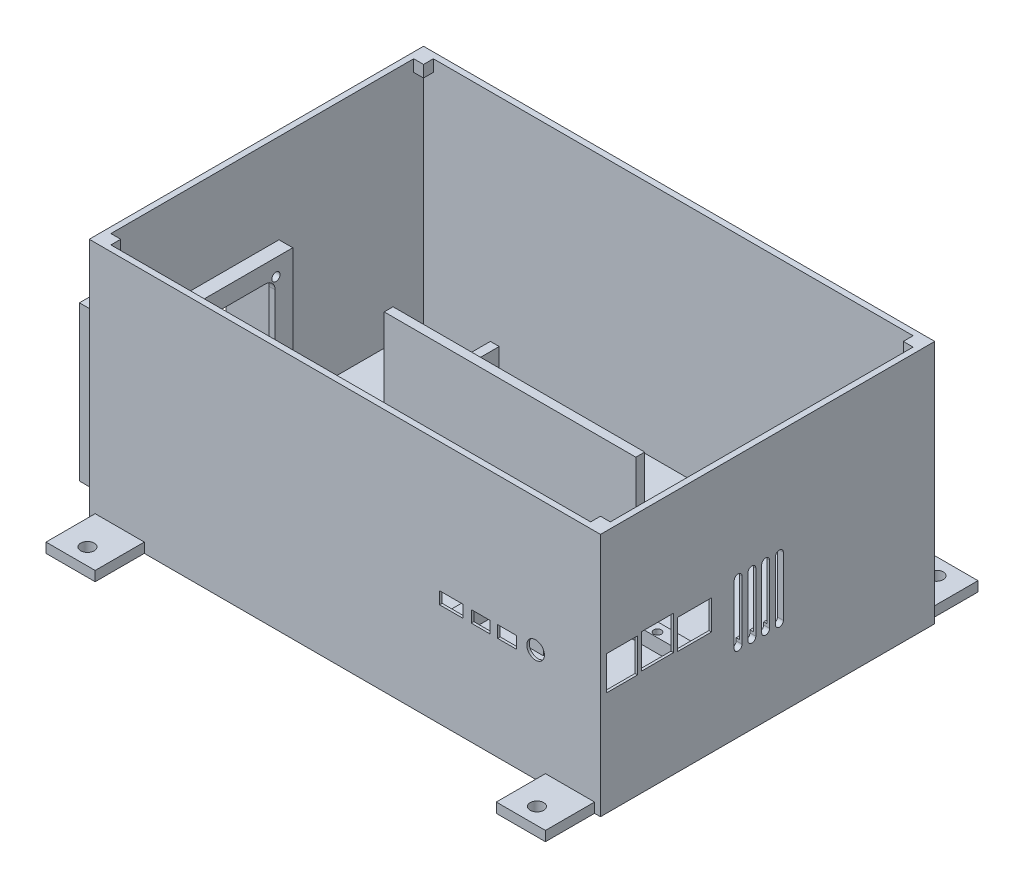
SolidWorks part; units mm, degrees
ref_plane "Front Plane" through (0, 0, 0) normal (0, 0, 1) x (1, 0, 0)
ref_plane "Top Plane" through (0, 0, 0) normal (0, 1, 0) x (1, 0, 0)
ref_plane "Right Plane" through (0, 0, 0) normal (1, 0, 0) x (0, 0, -1)
sketch "Sketch1" plane through (0, 0, 0) normal (0, 1, 0) x (1, 0, 0)
  line L1 (-130, -85) -> (130, -85)
  line L2 (-130, -85) -> (-130, 85)
  line L3 (-130, 85) -> (130, 85)
  line L4 (130, -85) -> (130, 85)
  line L5 (-130, -85) -> (130, 85) construction
  line L6 (-130, 85) -> (130, -85) construction
  point P0 (0, 0)
  dimension "D1" = 170
  dimension "D2" = 260
extrude "Floor" add sketch "Sketch1" along normal blind 4.3805
sketch "Sketch2" plane through (0, 4.3805, 0) normal (0, 1, 0) x (1, 0, 0)
  line L0 (127, -82) -> (127, 82)
  line L1 (127, 82) -> (-127, 82)
  line L2 (-127, 82) -> (-127, -82)
  line L3 (-127, -82) -> (127, -82)
  line L4 (130, -85) -> (130, 85)
  line L5 (130, 85) -> (-130, 85)
  line L6 (-130, 85) -> (-130, -85)
  line L7 (-130, -85) -> (130, -85)
  line L8 (130, -85) -> (130, 85)
  line L9 (130, 85) -> (-130, 85)
  line L10 (-130, 85) -> (-130, -85)
  line L11 (-130, -85) -> (130, -85)
  dimension "D1" = 0
  dimension "D2" = 3
extrude "Wall" add sketch "Sketch2" along normal blind 120
sketch "Sketch4" plane through (0, 4.3805, 0) normal (0, 1, 0) x (1, 0, 0)
  line L0 (120, -33) -> (49, -33)
  line L1 (127, -82) -> (42, -82)
  line L2 (127, -82) -> (127, -26)
  line L3 (127, -26) -> (42, -26)
  line L4 (42, -82) -> (42, -26)
  line L5 (49, -75) -> (49, -33)
  line L6 (120, -75) -> (49, -75)
  line L7 (120, -75) -> (120, -33)
  dimension "D1" = 85
  dimension "D2" = 56
  dimension "D3" = 7
extrude "Rpi stand" add sketch "Sketch4" along normal blind 7 from offset 30
sketch "Sketch7" plane through (0, 124.3805, 0) normal (0, 1, 0) x (1, 0, 0)
sketch "Sketch3" plane through (0, 0, 0) normal (0, 1, 0) x (1, 0, 0)
  line L0 (-114.3, 101.6) -> (114.3, 101.6) construction
  line L1 (-127, 85) -> (-102, 85)
  line L2 (-127, 85) -> (-127, 110)
  line L3 (-127, 110) -> (-102, 110)
  line L4 (-102, 85) -> (-102, 110)
  line L5 (127, 85) -> (102, 85)
  line L6 (127, 85) -> (127, 110)
  line L7 (127, 110) -> (102, 110)
  line L8 (102, 85) -> (102, 110)
  line L9 (-127, -85) -> (-102, -85)
  line L10 (-127, -85) -> (-127, -110)
  line L11 (-127, -110) -> (-102, -110)
  line L12 (-102, -85) -> (-102, -110)
  line L13 (127, -85) -> (102, -85)
  line L14 (127, -85) -> (127, -110)
  line L15 (127, -110) -> (102, -110)
  line L16 (102, -85) -> (102, -110)
  line L17 (114.3, 101.6) -> (114.3, -101.6) construction
  line L18 (114.3, -101.6) -> (-114.3, -101.6) construction
  line L19 (-114.3, -101.6) -> (-114.3, 101.6) construction
  line L20 (-130, 0) -> (130, 0) construction
  line L21 (130, 85) -> (-130, 85) construction
  line L22 (130, -85) -> (130, 85) construction
  line L23 (0, 101.6) -> (0, -101.6) construction
  line L26 (-130, 85) -> (-130, -85) construction
  line L27 (-130, -85) -> (130, -85) construction
  circle A0 centre (-114.3, 101.6) radius 3.429
  circle A1 centre (114.3, 101.6) radius 3.429
  circle A2 centre (114.3, -101.6) radius 3.429
  circle A3 centre (-114.3, -101.6) radius 3.429
  point P4 (-130, -85)
  point P9 (130, -85)
  point P28 (-114.5, -85)
  point P29 (-102, -97.5)
  point P30 (114.5, -85)
  point P31 (-102, 97.5)
  dimension "D5" = 6.858
  dimension "D1" = 25
  dimension "D2" = 25
  dimension "D3" = 25
  dimension "D6" = 203.2
  dimension "D7" = 228.6
  dimension "D8" = 3
  dimension "D9" = 3
  dimension "D4" = 25
extrude "Brackets" add sketch "Sketch3" along normal blind 5
sketch "Sketch5" plane through (-130, 0, 0) normal (-1, 0, 0) x (0, 0, 1)
  line L0 (-8.5, 78.8805) -> (70, 78.8805)
  line L1 (-1, 4.3805) -> (62.5, 4.3805)
  line L2 (-4.5, 7.8805) -> (-4.5, 71.3805)
  line L3 (-1, 74.8805) -> (62.5, 74.8805)
  line L4 (66, 7.8805) -> (66, 71.3805)
  line L5 (70, 0.3805) -> (70, 78.8805)
  line L6 (-8.5, 0.3805) -> (70, 0.3805)
  line L7 (-8.5, 0.3805) -> (-8.5, 78.8805)
  line L8 (-4.5, 4.3805) -> (66, 4.3805) construction
  line L9 (110, 5) -> (110, 0) construction
  line L10 (-4.5, 4.3805) -> (-4.5, 74.8805) construction
  line L11 (-82, 4.3805) -> (82, 4.3805) construction
  line L12 (66, 4.3805) -> (66, 74.8805) construction
  line L13 (-4.5, 74.8805) -> (66, 74.8805) construction
  arc A0 (-1, 4.3805) -> (-4.5, 7.8805) centre (-1, 7.8805) cw
  arc A1 (62.5, 4.3805) -> (66, 7.8805) centre (62.5, 7.8805) ccw
  arc A2 (62.5, 74.8805) -> (66, 71.3805) centre (62.5, 71.3805) cw
  arc A3 (-4.5, 71.3805) -> (-1, 74.8805) centre (-1, 71.3805) cw
  dimension "D4" = 3.5
  dimension "D1" = 70.5
  dimension "D2" = 70.5
  dimension "D5" = 40
  dimension "D3" = 4
extrude "Fan Holder" add sketch "Sketch5" along normal blind 20 and the other way blind 10
sketch "Sketch8" plane through (-130, 0, 0) normal (-1, 0, 0) x (0, 0, 1)
  line L4 (-4.5, 71.3805) -> (-4.5, 7.8805)
  line L5 (-1, 4.3805) -> (62.5, 4.3805)
  line L6 (66, 7.8805) -> (66, 71.3805)
  line L7 (62.5, 74.8805) -> (-1, 74.8805)
  line L8 (-4.5, 71.3805) -> (-4.5, 7.8805)
  line L9 (-1, 4.3805) -> (62.5, 4.3805)
  line L10 (66, 7.8805) -> (66, 71.3805)
  line L23 (62.5, 74.8805) -> (-1, 74.8805)
  arc A2 (-4.5, 7.8805) -> (-1, 4.3805) centre (-1, 7.8805) ccw
  arc A3 (-4.5, 7.8805) -> (-1, 4.3805) centre (-1, 7.8805) ccw
  arc A4 (62.5, 4.3805) -> (66, 7.8805) centre (62.5, 7.8805) ccw
  arc A5 (62.5, 4.3805) -> (66, 7.8805) centre (62.5, 7.8805) ccw
  arc A8 (66, 71.3805) -> (62.5, 74.8805) centre (62.5, 71.3805) ccw
  arc A14 (66, 71.3805) -> (62.5, 74.8805) centre (62.5, 71.3805) ccw
  arc A16 (-1, 74.8805) -> (-4.5, 71.3805) centre (-1, 71.3805) ccw
  arc A17 (-1, 74.8805) -> (-4.5, 71.3805) centre (-1, 71.3805) ccw
  dimension "D1" = 0
extrude "Fan hole" cut sketch "Sketch8" against normal up to next
sketch "Sketch11" plane through (-120, 0, 0) normal (-1, 0, 0) x (0, 0, 1)
  line L0 (-8.5, 39.6305) -> (70, 39.6305) construction
  line L1 (30.75, 78.8805) -> (30.75, 0.3805) construction
  line L3 (0.05, 8.9305) -> (61.45, 8.9305) construction
  line L4 (-8.5, 78.8805) -> (-8.5, 0.3805)
  line L5 (-8.5, 0.3805) -> (70, 0.3805)
  line L6 (70, 0.3805) -> (70, 78.8805)
  line L7 (70, 78.8805) -> (-8.5, 78.8805)
  line L8 (-8.5, 78.8805) -> (-8.5, 0.3805)
  line L9 (-8.5, 0.3805) -> (70, 0.3805)
  line L10 (70, 0.3805) -> (70, 78.8805)
  line L11 (70, 78.8805) -> (-8.5, 78.8805)
  line L12 (0.05, 8.9305) -> (0.05, 70.3305) construction
  line L13 (0.05, 70.3305) -> (61.45, 70.3305) construction
  line L14 (61.45, 8.9305) -> (61.45, 70.3305) construction
  line L15 (0.05, 8.9305) -> (61.45, 70.3305) construction
  line L16 (0.5, 69.8805) -> (0.5, 9.3805)
  line L17 (0.5, 9.3805) -> (61, 9.3805)
  line L18 (61, 9.3805) -> (61, 69.8805)
  line L19 (61, 69.8805) -> (0.5, 69.8805)
  line L20 (0.5, 64.8805) -> (0.5, 14.3805)
  line L21 (5.5, 9.3805) -> (56, 9.3805)
  line L22 (61, 14.3805) -> (61, 64.8805)
  line L23 (56, 69.8805) -> (5.5, 69.8805)
  line L24 (0.05, 70.3305) -> (61.45, 8.9305) construction
  arc A0 (0.5, 14.3805) -> (5.5, 9.3805) centre (5.5, 14.3805) ccw
  arc A1 (56, 9.3805) -> (61, 14.3805) centre (56, 14.3805) ccw
  arc A2 (61, 64.8805) -> (56, 69.8805) centre (56, 64.8805) ccw
  arc A3 (0.5, 64.8805) -> (5.5, 69.8805) centre (5.5, 64.8805) cw
  circle A4 centre (0.05, 70.3305) radius 2.1
  circle A5 centre (61.45, 70.3305) radius 2.1
  circle A6 centre (61.45, 8.9305) radius 2.1
  circle A7 centre (0.05, 8.9305) radius 2.1
  point P24 (30.75, 39.6305)
  point P34 (30.75, 39.6305)
  dimension "D3" = 5
  dimension "D6" = 4.2
  dimension "D4" = 61.4
  dimension "D5" = 61.4
  dimension "D1" = 0
  dimension "D2" = 9
extrude "Boss-Extrude9" add sketch "Sketch11" along normal blind 3
sketch "Sketch12" plane through (0, 34.3805, 0) normal (0, -1, 0) x (1, 0, 0)
  line L1 (42, 26) -> (49, 26)
  line L2 (42, 26) -> (42, 33)
  line L3 (42, 33) -> (49, 33)
  line L4 (49, 26) -> (49, 33)
  dimension "D1" = 7
  dimension "D2" = 7
extrude "Boss-Extrude10" add sketch "Sketch12" along normal up to next
sketch "Sketch13" plane through (0, 4.3805, 0) normal (0, 1, 0) x (1, 0, 0)
  line L0 (127, 82) -> (-127, 82) construction
  line L2 (-107, -57) -> (-107, 5.7) construction
  line L3 (-107, 5.7) -> (-69.4, 5.7) construction
  line L4 (-107, -57) -> (-69.4, -57) construction
  line L5 (-69.4, 5.7) -> (-69.4, -57) construction
  line L6 (-69.4, 5.7) -> (-57.4, 5.7) construction
  line L7 (-57.4, 5.7) -> (-57.4, -57) construction
  line L8 (-57.4, -57) -> (-19.8, -57) construction
  line L9 (-19.8, -57) -> (-19.8, 5.7) construction
  line L10 (-19.8, 5.7) -> (-57.4, 5.7) construction
  line L11 (-69.4, -57) -> (-57.4, -57) construction
  line L12 (-19.8, -57) -> (62.83, -57) construction
  line L13 (62.83, -57) -> (62.83, -25.4) construction
  line L14 (62.83, -25.4) -> (105, -25.4) construction
  line L15 (105, -25.4) -> (105, -57) construction
  line L16 (105, -57) -> (62.83, -57) construction
  line L17 (118, 82) -> (118, 21.5) construction
  line L18 (-16.3, -57.85) -> (-16.3, 6.55) construction
  line L20 (127, -82) -> (127, 82) construction
  line L21 (118, 21.5) -> (120.7, 21.5) construction
  line L22 (118, 21.5) -> (41.5, 21.5) construction
  line L23 (-6.3, -47) -> (30.69, -47) construction
  line L24 (-6.3, -47) -> (-6.3, -6.4) construction
  line L25 (-6.3, -6.4) -> (30.69, -6.4) construction
  line L26 (30.69, -47) -> (30.69, -6.4) construction
  line L27 (-6.3, -47) -> (30.69, -6.4) construction
  line L28 (-6.3, -6.4) -> (30.69, -47) construction
  line L29 (130, -85) -> (130, 85) construction
  line L30 (-127, -82) -> (127, -82) construction
  line L457 (-127, 8.5) -> (-127, -70) construction
  line L458 (-127, -82) -> (127, -82) construction
  circle A0 centre (-107, -57) radius 1.25
  circle A1 centre (-107, 5.7) radius 1.25
  circle A2 centre (-69.4, 5.7) radius 1.25
  circle A3 centre (-69.4, -57) radius 1.25
  circle A4 centre (-57.4, 5.7) radius 1.25
  circle A5 centre (-57.4, -57) radius 1.25
  circle A6 centre (-19.8, -57) radius 1.25
  circle A7 centre (-19.8, 5.7) radius 1.25
  circle A12 centre (120.7, 21.5) radius 1.25
  circle A13 centre (41.5, 21.5) radius 1.25
  circle A14 centre (-107, 5.7) radius 2.75
  circle A15 centre (-107, -57) radius 2.75
  circle A16 centre (-69.4, 5.7) radius 2.75
  circle A17 centre (-57.4, 5.7) radius 2.75
  circle A18 centre (-69.4, -57) radius 2.75
  circle A19 centre (-57.4, -57) radius 2.75
  circle A20 centre (-19.8, -57) radius 2.75
  circle A21 centre (-19.8, 5.7) radius 2.75
  circle A22 centre (62.83, -57) radius 2.5
  circle A23 centre (62.83, -25.4) radius 2.5
  circle A24 centre (105, -25.4) radius 2.5
  circle A25 centre (105, -57) radius 2.5
  circle A26 centre (-6.3, -47) radius 1.25
  circle A28 centre (-6.3, -47) radius 2.75
  circle A30 centre (-69.4, 5.7) radius 1.65 construction
  circle A31 centre (104.2333, -41.2) radius 1.5 construction
  circle A32 centre (104.2333, -41.2) radius 1.5 construction
  circle A33 centre (63.5933, -41.2) radius 1.5 construction
  circle A34 centre (63.5933, -41.2) radius 1.5 construction
  circle A35 centre (104.2333, -41.2) radius 3
  circle A36 centre (63.5933, -41.2) radius 3
  circle A37 centre (-6.3, -6.4) radius 1.25
  circle A38 centre (30.69, -6.4) radius 1.25
  circle A39 centre (30.69, -47) radius 1.25
  circle A40 centre (-6.3, -6.4) radius 2.75
  circle A41 centre (30.69, -6.4) radius 2.75
  circle A42 centre (30.69, -47) radius 2.75
  circle A43 centre (30.69, -6.4) radius 1.5 construction
  circle A44 centre (30.69, -6.4) radius 1.5 construction
  point P2 (-127, -82)
  point P3 (127, -82)
  point P8 (12.195, -26.7)
  point P31 (127, 82)
  point P32 (-127, 82)
  point P90 (-123, -62.5)
  point P91 (-123, -66)
  point P92 (-130, -70)
  point P93 (-130, 8.5)
  point P94 (-127, 8.5)
  point P95 (-127, -70)
  point P96 (-127, 8.5)
  point P97 (-120, 8.5)
  point P98 (-120, -70)
  point P99 (-127, -70)
  point P100 (-120, 8.5)
  point P101 (-120, -70)
  point P102 (-130, -85)
  point P103 (-127, -85)
  point P104 (-102, -85)
  point P105 (102, -85)
  point P106 (127, -85)
  point P107 (130, -85)
  point P108 (-130, 85)
  point P109 (-130, -85)
  point P110 (130, 85)
  point P111 (127, 85)
  point P112 (102, 85)
  point P113 (-102, 85)
  point P114 (-127, 85)
  point P115 (-130, 85)
  point P116 (130, -85)
  point P117 (130, 85)
  point P118 (-130, 85)
  point P119 (-130, -85)
  point P120 (130, 85)
  point P121 (-130, 85)
  point P122 (130, -85)
  point P123 (130, 85)
  point P124 (-130, -85)
  point P125 (130, -85)
  point P126 (-127, 82)
  point P127 (-127, -82)
  point P128 (127, 82)
  point P129 (-127, 82)
  point P130 (127, -82)
  point P131 (127, 82)
  point P132 (-127, -82)
  point P133 (127, -82)
  point P134 (-127, 82)
  point P135 (-127, 8.5)
  point P136 (-127, -70)
  point P137 (-127, -82)
  point P138 (127, -82)
  point P139 (127, 82)
  point P140 (42, -82)
  point P141 (127, -82)
  point P142 (42, -26)
  point P143 (42, -82)
  point P144 (127, -26)
  point P145 (42, -26)
  point P146 (127, -82)
  point P147 (127, -26)
  point P148 (42, -82)
  point P149 (127, -82)
  point P150 (42, -33)
  point P151 (42, -82)
  point P152 (127, -26)
  point P153 (49, -26)
  point P154 (127, -82)
  point P155 (127, -26)
  point P156 (49, -75)
  point P157 (120, -75)
  point P158 (49, -33)
  point P159 (49, -75)
  point P160 (120, -33)
  point P161 (49, -33)
  point P162 (120, -75)
  point P163 (120, -33)
  point P164 (49, -75)
  point P165 (120, -75)
  point P166 (49, -33)
  point P167 (49, -75)
  point P168 (120, -33)
  point P169 (49, -33)
  point P170 (120, -75)
  point P171 (120, -33)
  point P172 (-102, 110)
  point P173 (-127, 110)
  point P174 (-102, 85)
  point P175 (-102, 110)
  point P176 (-127, 85)
  point P177 (-102, 85)
  point P178 (-127, 110)
  point P179 (-127, 85)
  point P180 (-102, 110)
  point P181 (-127, 110)
  point P182 (-102, 85)
  point P183 (-102, 110)
  point P184 (-127, 110)
  point P185 (-127, 85)
  point P186 (-114.3, 101.6)
  point P187 (-111.0208, 102.6025)
  point P188 (-114.3, 101.6)
  point P189 (-111.0208, 102.6025)
  point P190 (114.3, 101.6)
  point P191 (117.5792, 102.6025)
  point P192 (114.3, 101.6)
  point P193 (117.5792, 102.6025)
  point P194 (127, 85)
  point P195 (127, 110)
  point P196 (127, 110)
  point P197 (102, 110)
  point P198 (102, 110)
  point P199 (102, 85)
  point P200 (127, 85)
  point P201 (127, 110)
  point P202 (127, 110)
  point P203 (102, 110)
  point P204 (102, 110)
  point P205 (102, 85)
  point P206 (102, 85)
  point P207 (127, 85)
  point P208 (-114.3, -101.6)
  point P209 (-111.0208, -100.5975)
  point P210 (-114.3, -101.6)
  point P211 (-111.0208, -100.5975)
  point P212 (-127, -85)
  point P213 (-127, -110)
  point P214 (-127, -110)
  point P215 (-102, -110)
  point P216 (-102, -110)
  point P217 (-102, -85)
  point P218 (-127, -85)
  point P219 (-127, -110)
  point P220 (-127, -110)
  point P221 (-102, -110)
  point P222 (-102, -110)
  point P223 (-102, -85)
  point P224 (-102, -85)
  point P225 (-127, -85)
  point P226 (114.3, -101.6)
  point P227 (117.5792, -100.5975)
  point P228 (114.3, -101.6)
  point P229 (117.5792, -100.5975)
  point P230 (127, -110)
  point P231 (127, -85)
  point P232 (102, -85)
  point P233 (102, -110)
  point P234 (102, -110)
  point P235 (127, -110)
  point P236 (127, -110)
  point P237 (127, -85)
  point P238 (127, -85)
  point P239 (102, -85)
  point P240 (102, -85)
  point P241 (102, -110)
  point P242 (102, -110)
  point P243 (127, -110)
  point P244 (-130, 8.5)
  point P245 (-130, -70)
  point P246 (-120, 8.5)
  point P247 (-127, 8.5)
  point P248 (-130, 8.5)
  point P249 (-150, 8.5)
  point P250 (-120, -70)
  point P251 (-127, -70)
  point P252 (-130, -70)
  point P253 (-150, -70)
  point P254 (-130, -70)
  point P255 (-150, -70)
  point P256 (-130, 8.5)
  point P257 (-150, 8.5)
  point P258 (-120, -70)
  point P259 (-120, 8.5)
  point P260 (-123, 4.5)
  point P261 (-150, 4.5)
  point P262 (-123, 4.5)
  point P263 (-150, 4.5)
  point P264 (-123, 1)
  point P265 (-150, 1)
  point P266 (-123, -62.5)
  point P267 (-150, -62.5)
  point P268 (-123, -66)
  point P269 (-150, -66)
  point P270 (-123, -66)
  point P271 (-150, -66)
  point P272 (-123, -62.5)
  point P273 (-150, -62.5)
  point P274 (-123, 1)
  point P275 (-150, 1)
  point P276 (-150, -70)
  point P277 (-150, 8.5)
  point P278 (-150, 8.5)
  point P279 (-150, -70)
  point P280 (-150, 4.5)
  point P281 (-150, 1)
  point P282 (-150, -62.5)
  point P283 (-150, 1)
  point P284 (-150, -62.5)
  point P285 (-150, -66)
  point P286 (-150, -62.5)
  point P287 (-150, -66)
  point P288 (-150, 1)
  point P289 (-150, -62.5)
  point P290 (-150, 4.5)
  point P291 (-150, 1)
  point P292 (-123, 4.5)
  point P293 (-123, 1)
  point P294 (-123, -62.5)
  point P295 (-123, 1)
  point P296 (-123, 4.5)
  point P297 (-123, 1)
  point P298 (-123, 1)
  point P299 (-123, -62.5)
  point P300 (-123, -62.5)
  point P301 (-123, -66)
  point P302 (-123, -5.5)
  point P303 (-120, -5.5)
  point P304 (-123, -56)
  point P305 (-120, -56)
  point P306 (-123, -61)
  point P307 (-120, -61)
  point P308 (-123, -61)
  point P309 (-120, -61)
  point P310 (-123, -56)
  point P311 (-120, -56)
  point P312 (-123, -5.5)
  point P313 (-120, -5.5)
  point P314 (-123, -0.5)
  point P315 (-120, -0.5)
  point P316 (-123, -0.5)
  point P317 (-120, -0.5)
  point P318 (-123, -0.5)
  point P319 (-123, -5.5)
  point P320 (-123, -56)
  point P321 (-123, -5.5)
  point P322 (-123, -56)
  point P323 (-123, -61)
  point P324 (-123, -56)
  point P325 (-123, -61)
  point P326 (-123, -5.5)
  point P327 (-123, -56)
  point P328 (-123, -0.5)
  point P329 (-123, -5.5)
  point P330 (-120, -5.5)
  point P331 (-120, -0.5)
  point P332 (-120, -56)
  point P333 (-120, -5.5)
  point P334 (-120, -61)
  point P335 (-120, -56)
  point P336 (-120, -61)
  point P337 (-120, -56)
  point P338 (-120, -5.5)
  point P339 (-120, -56)
  point P340 (-120, -5.5)
  point P341 (-120, -0.5)
  point P342 (-123, 2.05)
  point P343 (-123, -2.15)
  point P344 (-120, -2.15)
  point P345 (-120, 2.05)
  point P346 (-123, -59.35)
  point P347 (-123, -63.55)
  point P348 (-120, -63.55)
  point P349 (-120, -59.35)
  point P350 (-123, -59.35)
  point P351 (-123, -63.55)
  point P352 (-120, -63.55)
  point P353 (-120, -59.35)
  point P354 (-123, 2.05)
  point P355 (-123, -2.15)
  point P356 (-120, -2.15)
  point P357 (-120, 2.05)
  point P358 (49, -33)
  point P359 (42, -33)
  point P360 (49, -26)
  point P361 (49, -33)
  point P362 (42, -33)
  point P363 (42, -26)
  point P364 (42, -26)
  point P365 (49, -26)
  point P366 (49, -26)
  point P367 (49, -33)
  point P368 (49, -33)
  point P369 (42, -33)
  point P370 (-130, -85)
  point P371 (130, -85)
  point P372 (-130, -85)
  point P373 (-130, 85)
  point P374 (-130, 85)
  point P375 (130, 85)
  point P376 (130, -85)
  point P377 (130, 85)
  point P378 (-130, -85)
  point P379 (130, 85)
  point P380 (-130, 85)
  point P381 (130, -85)
  point P382 (127, -82)
  point P383 (127, 82)
  point P384 (127, 82)
  point P385 (-127, 82)
  point P386 (-127, 82)
  point P387 (-127, -82)
  point P388 (-127, -82)
  point P389 (127, -82)
  point P390 (130, -85)
  point P391 (130, 85)
  point P392 (130, 85)
  point P393 (-130, 85)
  point P394 (-130, 85)
  point P395 (-130, -85)
  point P396 (-130, -85)
  point P397 (130, -85)
  point P398 (130, -85)
  point P399 (130, 85)
  point P400 (130, 85)
  point P401 (-130, 85)
  point P402 (-130, 85)
  point P403 (-130, -85)
  point P404 (-130, -85)
  point P405 (130, -85)
  point P406 (120, -33)
  point P407 (49, -33)
  point P408 (127, -82)
  point P409 (42, -82)
  point P410 (127, -82)
  point P411 (127, -26)
  point P412 (127, -26)
  point P413 (42, -26)
  point P414 (42, -82)
  point P415 (42, -26)
  point P416 (49, -75)
  point P417 (49, -33)
  point P418 (120, -75)
  point P419 (49, -75)
  point P420 (120, -75)
  point P421 (120, -33)
  point P422 (-114.3, 101.6)
  point P423 (114.3, 101.6)
  point P424 (-127, 85)
  point P425 (-102, 85)
  point P426 (-127, 85)
  point P427 (-127, 110)
  point P428 (-127, 110)
  point P429 (-102, 110)
  point P430 (-102, 85)
  point P431 (-102, 110)
  point P432 (127, 85)
  point P433 (102, 85)
  point P434 (127, 85)
  point P435 (127, 110)
  point P436 (127, 110)
  point P437 (102, 110)
  point P438 (102, 85)
  point P439 (102, 110)
  point P440 (-127, -85)
  point P441 (-102, -85)
  point P442 (-127, -85)
  point P443 (-127, -110)
  point P444 (-127, -110)
  point P445 (-102, -110)
  point P446 (-102, -85)
  point P447 (-102, -110)
  point P448 (127, -85)
  point P449 (102, -85)
  point P450 (127, -85)
  point P451 (127, -110)
  point P452 (127, -110)
  point P453 (102, -110)
  point P454 (102, -85)
  point P455 (102, -110)
  point P456 (114.3, 101.6)
  point P457 (114.3, -101.6)
  point P458 (114.3, -101.6)
  point P459 (-114.3, -101.6)
  point P460 (-114.3, -101.6)
  point P461 (-114.3, 101.6)
  point P462 (-130, 0)
  point P463 (130, 0)
  point P464 (130, 85)
  point P465 (-130, 85)
  point P466 (130, -85)
  point P467 (130, 85)
  point P468 (0, 101.6)
  point P469 (0, -101.6)
  point P470 (-130, 85)
  point P471 (-130, -85)
  point P472 (-130, -85)
  point P473 (130, -85)
  point P474 (-130, 8.5)
  point P475 (-130, -70)
  point P476 (-130, 1)
  point P477 (-130, -62.5)
  point P478 (-130, 1)
  point P479 (-130, -62.5)
  point P480 (-130, 8.5)
  point P481 (-130, -70)
  point P482 (-130, 4.5)
  point P483 (-130, -66)
  point P484 (-130, 82)
  point P485 (-130, -82)
  point P486 (-130, 4.5)
  point P487 (-130, -66)
  point P488 (-130, 1)
  point P489 (-130, -62.5)
  point P490 (-130, -62.5)
  point P491 (-130, 1)
  point P492 (-130, 1)
  point P493 (-130, -62.5)
  point P494 (-130, -62.5)
  point P495 (-130, 1)
  point P496 (-120, 8.5)
  point P497 (-120, -70)
  point P498 (-120, -0.05)
  point P499 (-120, -61.45)
  point P500 (-120, 8.5)
  point P501 (-120, -70)
  point P502 (-120, -70)
  point P503 (-120, 8.5)
  point P504 (-120, 8.5)
  point P505 (-120, -70)
  point P506 (-120, -70)
  point P507 (-120, 8.5)
  point P508 (-120, -0.05)
  point P509 (-120, -61.45)
  point P510 (-120, -0.05)
  point P511 (-120, -61.45)
  point P512 (-120, -0.5)
  point P513 (-120, -61)
  point P514 (-120, -61)
  point P515 (-120, -0.5)
  point P516 (-120, -5.5)
  point P517 (-120, -56)
  point P518 (-120, -56)
  point P519 (-120, -5.5)
  point P520 (-120, -0.05)
  point P521 (-120, -61.45)
  point P522 (42, -26)
  point P523 (49, -26)
  point P524 (42, -26)
  point P525 (42, -33)
  point P526 (42, -33)
  point P527 (49, -33)
  point P528 (49, -26)
  point P529 (49, -33)
  point P530 (-123, -62.5)
  point P531 (-123, -66)
  point P532 (-130, -70)
  point P533 (-130, 8.5)
  point P534 (-127, 8.5)
  point P535 (-127, -70)
  point P536 (-127, 8.5)
  point P537 (-120, 8.5)
  point P538 (-120, -70)
  point P539 (-127, -70)
  point P540 (-120, 8.5)
  point P541 (-120, -70)
  point P542 (-130, -85)
  point P543 (-127, -85)
  point P544 (-102, -85)
  point P545 (102, -85)
  point P546 (127, -85)
  point P547 (130, -85)
  point P548 (-130, 85)
  point P549 (-130, -85)
  point P550 (130, 85)
  point P551 (127, 85)
  point P552 (102, 85)
  point P553 (-102, 85)
  point P554 (-127, 85)
  point P555 (-130, 85)
  point P556 (130, -85)
  point P557 (130, 85)
  point P558 (-130, 85)
  point P559 (-130, -85)
  point P560 (130, 85)
  point P561 (-130, 85)
  point P562 (130, -85)
  point P563 (130, 85)
  point P564 (-130, -85)
  point P565 (130, -85)
  point P566 (-127, 82)
  point P567 (-127, -82)
  point P568 (127, 82)
  point P569 (-127, 82)
  point P570 (127, -82)
  point P571 (127, 82)
  point P572 (-127, -82)
  point P573 (127, -82)
  point P574 (-127, 82)
  point P575 (-127, 8.5)
  point P576 (-127, -70)
  point P577 (-127, -82)
  point P578 (127, 82)
  point P579 (-127, 82)
  point P580 (127, -82)
  point P581 (127, 82)
  point P582 (-127, -82)
  point P583 (127, -82)
  point P584 (42, -82)
  point P585 (127, -82)
  point P586 (42, -26)
  point P587 (42, -82)
  point P588 (127, -26)
  point P589 (42, -26)
  point P590 (127, -82)
  point P591 (127, -26)
  point P592 (42, -82)
  point P593 (127, -82)
  point P594 (42, -33)
  point P595 (42, -82)
  point P596 (127, -26)
  point P597 (49, -26)
  point P598 (127, -82)
  point P599 (127, -26)
  point P600 (49, -75)
  point P601 (120, -75)
  point P602 (49, -33)
  point P603 (49, -75)
  point P604 (120, -33)
  point P605 (49, -33)
  point P606 (120, -75)
  point P607 (120, -33)
  point P608 (49, -75)
  point P609 (120, -75)
  point P610 (49, -33)
  point P611 (49, -75)
  point P612 (120, -33)
  point P613 (49, -33)
  point P614 (120, -75)
  point P615 (120, -33)
  point P616 (-102, 110)
  point P617 (-127, 110)
  point P618 (-102, 85)
  point P619 (-102, 110)
  point P620 (-127, 85)
  point P621 (-102, 85)
  point P622 (-127, 110)
  point P623 (-127, 85)
  point P624 (-102, 110)
  point P625 (-127, 110)
  point P626 (-102, 85)
  point P627 (-102, 110)
  point P628 (-127, 110)
  point P629 (-127, 85)
  point P630 (-114.3, 101.6)
  point P631 (-111.0208, 102.6025)
  point P632 (-114.3, 101.6)
  point P633 (-111.0208, 102.6025)
  point P634 (114.3, 101.6)
  point P635 (117.5792, 102.6025)
  point P636 (114.3, 101.6)
  point P637 (117.5792, 102.6025)
  point P638 (127, 85)
  point P639 (127, 110)
  point P640 (127, 110)
  point P641 (102, 110)
  point P642 (102, 110)
  point P643 (102, 85)
  point P644 (127, 85)
  point P645 (127, 110)
  point P646 (127, 110)
  point P647 (102, 110)
  point P648 (102, 110)
  point P649 (102, 85)
  point P650 (102, 85)
  point P651 (127, 85)
  point P652 (-114.3, -101.6)
  point P653 (-111.0208, -100.5975)
  point P654 (-114.3, -101.6)
  point P655 (-111.0208, -100.5975)
  point P656 (-127, -85)
  point P657 (-127, -110)
  point P658 (-127, -110)
  point P659 (-102, -110)
  point P660 (-102, -110)
  point P661 (-102, -85)
  point P662 (-127, -85)
  point P663 (-127, -110)
  point P664 (-127, -110)
  point P665 (-102, -110)
  point P666 (-102, -110)
  point P667 (-102, -85)
  point P668 (-102, -85)
  point P669 (-127, -85)
  point P670 (114.3, -101.6)
  point P671 (117.5792, -100.5975)
  point P672 (114.3, -101.6)
  point P673 (117.5792, -100.5975)
  point P674 (127, -110)
  point P675 (127, -85)
  point P676 (102, -85)
  point P677 (102, -110)
  point P678 (102, -110)
  point P679 (127, -110)
  point P680 (127, -110)
  point P681 (127, -85)
  point P682 (127, -85)
  point P683 (102, -85)
  point P684 (102, -85)
  point P685 (102, -110)
  point P686 (102, -110)
  point P687 (127, -110)
  point P688 (-130, 8.5)
  point P689 (-130, -70)
  point P690 (-120, 8.5)
  point P691 (-127, 8.5)
  point P692 (-130, 8.5)
  point P693 (-150, 8.5)
  point P694 (-120, -70)
  point P695 (-127, -70)
  point P696 (-130, -70)
  point P697 (-150, -70)
  point P698 (-130, -70)
  point P699 (-150, -70)
  point P700 (-130, 8.5)
  point P701 (-150, 8.5)
  point P702 (-120, -70)
  point P703 (-120, 8.5)
  point P704 (-123, 4.5)
  point P705 (-150, 4.5)
  point P706 (-123, 4.5)
  point P707 (-150, 4.5)
  point P708 (-123, 1)
  point P709 (-150, 1)
  point P710 (-123, -62.5)
  point P711 (-150, -62.5)
  point P712 (-123, -66)
  point P713 (-150, -66)
  point P714 (-123, -66)
  point P715 (-150, -66)
  point P716 (-123, -62.5)
  point P717 (-150, -62.5)
  point P718 (-123, 1)
  point P719 (-150, 1)
  point P720 (-150, -70)
  point P721 (-150, 8.5)
  point P722 (-150, 8.5)
  point P723 (-150, -70)
  point P724 (-150, 4.5)
  point P725 (-150, 1)
  point P726 (-150, -62.5)
  point P727 (-150, 1)
  point P728 (-150, -62.5)
  point P729 (-150, -66)
  point P730 (-150, -62.5)
  point P731 (-150, -66)
  point P732 (-150, 1)
  point P733 (-150, -62.5)
  point P734 (-150, 4.5)
  point P735 (-150, 1)
  point P736 (-123, 4.5)
  point P737 (-123, 1)
  point P738 (-123, -62.5)
  point P739 (-123, 1)
  point P740 (-123, 4.5)
  point P741 (-123, 1)
  point P742 (-123, 1)
  point P743 (-123, -62.5)
  point P744 (-123, -62.5)
  point P745 (-123, -66)
  point P746 (-123, -5.5)
  point P747 (-120, -5.5)
  point P748 (-123, -56)
  point P749 (-120, -56)
  point P750 (-123, -61)
  point P751 (-120, -61)
  point P752 (-123, -61)
  point P753 (-120, -61)
  point P754 (-123, -56)
  point P755 (-120, -56)
  point P756 (-123, -5.5)
  point P757 (-120, -5.5)
  point P758 (-123, -0.5)
  point P759 (-120, -0.5)
  point P760 (-123, -0.5)
  point P761 (-120, -0.5)
  point P762 (-123, -0.5)
  point P763 (-123, -5.5)
  point P764 (-123, -56)
  point P765 (-123, -5.5)
  point P766 (-123, -56)
  point P767 (-123, -61)
  point P768 (-123, -56)
  point P769 (-123, -61)
  point P770 (-123, -5.5)
  point P771 (-123, -56)
  point P772 (-123, -0.5)
  point P773 (-123, -5.5)
  point P774 (-120, -5.5)
  point P775 (-120, -0.5)
  point P776 (-120, -56)
  point P777 (-120, -5.5)
  point P778 (-120, -61)
  point P779 (-120, -56)
  point P780 (-120, -61)
  point P781 (-120, -56)
  point P782 (-120, -5.5)
  point P783 (-120, -56)
  point P784 (-120, -5.5)
  point P785 (-120, -0.5)
  point P786 (-123, 2.05)
  point P787 (-123, -2.15)
  point P788 (-120, -2.15)
  point P789 (-120, 2.05)
  point P790 (-123, -59.35)
  point P791 (-123, -63.55)
  point P792 (-120, -63.55)
  point P793 (-120, -59.35)
  point P794 (-123, -59.35)
  point P795 (-123, -63.55)
  point P796 (-120, -63.55)
  point P797 (-120, -59.35)
  point P798 (-123, 2.05)
  point P799 (-123, -2.15)
  point P800 (-120, -2.15)
  point P801 (-120, 2.05)
  point P802 (49, -33)
  point P803 (42, -33)
  point P804 (49, -26)
  point P805 (49, -33)
  point P806 (42, -33)
  point P807 (42, -26)
  point P808 (42, -26)
  point P809 (49, -26)
  point P810 (49, -26)
  point P811 (49, -33)
  point P812 (49, -33)
  point P813 (42, -33)
  point P814 (-130, -85)
  point P815 (130, -85)
  point P816 (-130, -85)
  point P817 (-130, 85)
  point P818 (-130, 85)
  point P819 (130, 85)
  point P820 (130, -85)
  point P821 (130, 85)
  point P822 (-130, -85)
  point P823 (130, 85)
  point P824 (-130, 85)
  point P825 (130, -85)
  point P826 (127, -82)
  point P827 (127, 82)
  point P828 (127, 82)
  point P829 (-127, 82)
  point P830 (-127, 82)
  point P831 (-127, -82)
  point P832 (-127, -82)
  point P833 (127, -82)
  point P834 (130, -85)
  point P835 (130, 85)
  point P836 (130, 85)
  point P837 (-130, 85)
  point P838 (-130, 85)
  point P839 (-130, -85)
  point P840 (-130, -85)
  point P841 (130, -85)
  point P842 (130, -85)
  point P843 (130, 85)
  point P844 (130, 85)
  point P845 (-130, 85)
  point P846 (-130, 85)
  point P847 (-130, -85)
  point P848 (-130, -85)
  point P849 (130, -85)
  point P850 (120, -33)
  point P851 (49, -33)
  point P852 (127, -82)
  point P853 (42, -82)
  point P854 (127, -82)
  point P855 (127, -26)
  point P856 (127, -26)
  point P857 (42, -26)
  point P858 (42, -82)
  point P859 (42, -26)
  point P860 (49, -75)
  point P861 (49, -33)
  point P862 (120, -75)
  point P863 (49, -75)
  point P864 (120, -75)
  point P865 (120, -33)
  point P866 (-114.3, 101.6)
  point P867 (114.3, 101.6)
  point P868 (-127, 85)
  point P869 (-102, 85)
  point P870 (-127, 85)
  point P871 (-127, 110)
  point P872 (-127, 110)
  point P873 (-102, 110)
  point P874 (-102, 85)
  point P875 (-102, 110)
  point P876 (127, 85)
  point P877 (102, 85)
  point P878 (127, 85)
  point P879 (127, 110)
  point P880 (127, 110)
  point P881 (102, 110)
  point P882 (102, 85)
  point P883 (102, 110)
  point P884 (-127, -85)
  point P885 (-102, -85)
  point P886 (-127, -85)
  point P887 (-127, -110)
  point P888 (-127, -110)
  point P889 (-102, -110)
  point P890 (-102, -85)
  point P891 (-102, -110)
  point P892 (127, -85)
  point P893 (102, -85)
  point P894 (127, -85)
  point P895 (127, -110)
  point P896 (127, -110)
  point P897 (102, -110)
  point P898 (102, -85)
  point P899 (102, -110)
  point P900 (114.3, 101.6)
  point P901 (114.3, -101.6)
  point P902 (114.3, -101.6)
  point P903 (-114.3, -101.6)
  point P904 (-114.3, -101.6)
  point P905 (-114.3, 101.6)
  point P906 (-130, 0)
  point P907 (130, 0)
  point P908 (130, 85)
  point P909 (-130, 85)
  point P910 (130, -85)
  point P911 (130, 85)
  point P912 (0, 101.6)
  point P913 (0, -101.6)
  point P914 (-130, 85)
  point P915 (-130, -85)
  point P916 (-130, -85)
  point P917 (130, -85)
  point P918 (-130, 8.5)
  point P919 (-130, -70)
  point P920 (-130, 1)
  point P921 (-130, -62.5)
  point P922 (-130, 1)
  point P923 (-130, -62.5)
  point P924 (-130, 8.5)
  point P925 (-130, -70)
  point P926 (-130, 4.5)
  point P927 (-130, -66)
  point P928 (-130, 82)
  point P929 (-130, -82)
  point P930 (-130, 4.5)
  point P931 (-130, -66)
  point P932 (-130, 1)
  point P933 (-130, -62.5)
  point P934 (-130, -62.5)
  point P935 (-130, 1)
  point P936 (-130, 1)
  point P937 (-130, -62.5)
  point P938 (-130, -62.5)
  point P939 (-130, 1)
  point P940 (-120, 8.5)
  point P941 (-120, -70)
  point P942 (-120, -0.05)
  point P943 (-120, -61.45)
  point P944 (-120, 8.5)
  point P945 (-120, -70)
  point P946 (-120, -70)
  point P947 (-120, 8.5)
  point P948 (-120, 8.5)
  point P949 (-120, -70)
  point P950 (-120, -70)
  point P951 (-120, 8.5)
  point P952 (-120, -0.05)
  point P953 (-120, -61.45)
  point P954 (-120, -0.05)
  point P955 (-120, -61.45)
  point P956 (-120, -0.5)
  point P957 (-120, -61)
  point P958 (-120, -61)
  point P959 (-120, -0.5)
  point P960 (-120, -5.5)
  point P961 (-120, -56)
  point P962 (-120, -56)
  point P963 (-120, -5.5)
  point P964 (-120, -0.05)
  point P965 (-120, -61.45)
  point P966 (42, -26)
  point P967 (49, -26)
  point P968 (42, -26)
  point P969 (42, -33)
  point P970 (42, -33)
  point P971 (49, -33)
  point P972 (49, -26)
  point P973 (49, -33)
  dimension "D3" = 2.5
  dimension "D6" = 1.5
  dimension "D7" = 2.5
  dimension "D8" = 10
  dimension "D11" = 35
  dimension "D12" = 20
  dimension "D13" = 25
  dimension "D25" = 2.5
  dimension "D27" = 2.5
  dimension "D4" = 5
  dimension "D5" = 25
  dimension "D9" = 12
  dimension "D10" = 1.5
  dimension "D17" = 31.6
  dimension "D19" = 42.17
  dimension "D22" = 60.5
  dimension "D23" = 9
  dimension "D24" = 2.7
  dimension "D26" = 76.5
  dimension "D28" = 1.5
extrude "Built in Standoffs" add sketch "Sketch13" along normal blind 5 contours A1 | A16 A2 | A2 | A17 A4 | A4 | A14 A1 | A21 A7 | A7 | A15 A0 | A0 | A18 A3 | A3 | A19 A5 | A5 | A20 A6 | A6 | A22 | A23 | A24 A32 | A32 | A25 | A36 | A35 | A28 A26 | A26 | A40 A37 | A37 | A41 A38 | A38 | A42 A39 | A39 region at (-107, 4.3805, 57) region at (-107, 4.3805, -5.7) region at (-69.4, 4.3805, -5.7) region at (-69.4, 4.3805, 57) region at (-57.4, 4.3805, -5.7) region at (-57.4, 4.3805, 57) region at (-19.8, 4.3805, 57) region at (-19.8, 4.3805, -5.7) region at (-109.6722, 4.3805, -5.7) region at (-109.6722, 4.3805, 57) region at (-72.0722, 4.3805, -5.7) region at (-60.0722, 4.3805, -5.7) region at (-72.0722, 4.3805, 57) region at (-60.0722, 4.3805, 57) region at (-22.4722, 4.3805, 57) region at (-22.4722, 4.3805, -5.7) region at (62.83, 4.3805, 57) region at (62.83, 4.3805, 25.4) region at (105, 4.3805, 25.4) region at (105, 4.3805, 57) region at (-6.3, 4.3805, 47) region at (-8.9722, 4.3805, 47) region at (104.2333, 4.3805, 41.2) region at (101.3181, 4.3805, 41.2) region at (63.5933, 4.3805, 41.2) region at (-6.3, 4.3805, 6.4) region at (30.69, 4.3805, 6.4) region at (30.69, 4.3805, 47) region at (-8.9722, 4.3805, 6.4) region at (28.0178, 4.3805, 6.4) region at (28.0178, 4.3805, 47)
sketch "Sketch19" plane through (0, 9.3805, 0) normal (0, 1, 0) x (1, 0, 0)
  circle A0 centre (104.2333, -41.2) radius 1.25
  circle A1 centre (63.5933, -41.2) radius 1.25
  dimension "D1" = 2.5
  dimension "D2" = 2.5
extrude "Bread board holes" cut sketch "Sketch19" against normal blind 7
sketch "Sketch14" plane through (0, 4.3805, 0) normal (0, 1, 0) x (1, 0, 0)
  line L0 (127, 82) -> (-88, 82)
  line L1 (127, 82) -> (-127, 82) construction
  line L2 (-88, 82) -> (-88, 32)
  line L3 (-88, 32) -> (127, 32)
  line L4 (127, -82) -> (127, 82) construction
  line L5 (127, 32) -> (127, 82)
  dimension "D1" = 215
  dimension "D2" = 50
extrude "Screw Holes" cut sketch "Sketch13<4>" against normal blind 7 from surface contours A37 | A38 | A26 | A39 | A1 | A0 | A3 | A5 | A2 | A4 | A7 | A6 | A32 region at (-6.3, 4.3805, 47) region at (-6.3, 4.3805, 6.4) region at (30.69, 4.3805, 6.4) region at (30.69, 4.3805, 47) starting at face at (-107, 9.3805, -2.95)
sketch "Sketch13<4>" plane through (0, 4.3805, 0) normal (0, 1, 0) x (1, 0, 0) same geometry as "Sketch13"
extrude "Driver Screw Holes" cut sketch "Sketch13<5>" against normal blind 3 contours A13 | A12
sketch "Sketch13<5>" plane through (0, 4.3805, 0) normal (0, 1, 0) x (1, 0, 0) same geometry as "Sketch13"
sketch "Sketch16" plane through (0, 4.3805, 0) normal (0, 1, 0) x (1, 0, 0)
  line L0 (-93, 82) -> (-93, 28)
  line L1 (-93, 28) -> (35, 28)
  line L2 (-88.5, 82) -> (-88.5, 32.5)
  line L3 (-88.5, 32.5) -> (35, 32.5)
  line L10 (-88, 82) -> (-88, 33) construction
  line L11 (-88, 33) -> (29.1074, 33) construction
  line L14 (-93, 28) -> (127, 28) construction
  line L16 (-88, 33) -> (127, 33) construction
  line L17 (-88.5, 82) -> (-93, 82)
  line L20 (35, 28) -> (35, 32.5)
  line L21 (-88.5, 32.5) -> (29.1074, 32.5) construction
  line L25 (-88, 33) -> (127, 33)
  line L26 (127, 33) -> (127, 82)
  line L27 (127, 82) -> (-88, 82)
  line L28 (-88, 82) -> (-88, 33)
  line L29 (-88, 33) -> (127, 33) construction
  line L30 (127, 33) -> (127, 82) construction
  line L31 (127, 82) -> (-88, 82) construction
  line L32 (-88, 82) -> (-88, 33) construction
  line L57 (-88, 82) -> (-88, 33) construction
  line L58 (127, 82) -> (-127, 82) construction
  dimension "D3" = 0.5
  dimension "D5" = 128
  dimension "D1" = 0
  dimension "D2" = 5
extrude "Power supply wall" add sketch "Sketch16" along normal blind 10 contours L2 L3 L20 L1 L0 L17
sketch "Sketch25" plane through (0, 14.3805, 0) normal (0, 1, 0) x (1, 0, 0)
  line L0 (-93, 82) -> (-93, 28) construction
  line L1 (35, 28) -> (-93, 28)
  line L2 (35, 28) -> (35, 32.5)
  line L3 (35, 32.5) -> (-93, 32.5)
  line L4 (-93, 28) -> (-93, 32.5)
  line L5 (-88.5, 32.5) -> (35, 32.5) construction
  line L6 (-88.5, 32.5) -> (35, 32.5) construction
extrude "Boss-Extrude11" add sketch "Sketch25" along normal blind 40
sketch "Sketch17" plane through (0, 41.3805, 0) normal (0, 1, 0) x (1, 0, 0)
  circle A0 centre (46.5, -30.5) radius 1.9431
  circle A1 centre (104.5, -30.5) radius 1.9431
  circle A2 centre (104.5, -79.5) radius 1.9431
  circle A3 centre (46.5, -79.5) radius 1.9431
  dimension "D1" = 3.8862
extrude "Cut-Extrude3" cut sketch "Sketch17" against normal blind 3.4
sketch "Sketch20" plane through (0, 0, 85) normal (0, 0, 1) x (1, 0, 0)
  line L1 (49.6827, 57.1504) -> (58.6882, 57.1504) construction
  line L2 (49.6827, 57.1504) -> (49.6827, 53.9554) construction
  line L3 (49.6827, 53.9554) -> (58.6882, 53.9554) construction
  line L4 (58.6882, 57.1504) -> (58.6882, 53.9554) construction
  line L5 (79.2167, 56.9908) -> (85.8798, 56.9908) construction
  line L6 (79.2167, 56.9908) -> (79.2167, 53.9258) construction
  line L7 (79.2167, 53.9258) -> (85.8798, 53.9258) construction
  line L8 (85.8798, 56.9908) -> (85.8798, 53.9258) construction
  line L9 (65.7798, 56.9112) -> (72.2962, 56.9112) construction
  line L10 (65.7798, 56.9112) -> (65.7798, 53.9475) construction
  line L11 (65.7798, 53.9475) -> (72.2962, 53.9475) construction
  line L12 (72.2962, 56.9112) -> (72.2962, 53.9475) construction
  line L13 (48.1827, 58.6504) -> (60.1882, 58.6504)
  line L14 (60.1882, 58.6504) -> (60.1882, 52.4554)
  line L15 (48.1827, 52.4554) -> (60.1882, 52.4554)
  line L16 (48.1827, 58.6504) -> (48.1827, 52.4554)
  line L17 (77.7167, 58.4908) -> (87.3798, 58.4908)
  line L18 (87.3798, 58.4908) -> (87.3798, 52.4258)
  line L19 (77.7167, 52.4258) -> (87.3798, 52.4258)
  line L20 (77.7167, 58.4908) -> (77.7167, 52.4258)
  line L21 (64.2798, 58.4112) -> (73.7962, 58.4112)
  line L22 (73.7962, 58.4112) -> (73.7962, 52.4475)
  line L23 (64.2798, 52.4475) -> (73.7962, 52.4475)
  line L24 (64.2798, 58.4112) -> (64.2798, 52.4475)
  circle A0 centre (97, 56.9705) radius 4.5
  dimension "D1" = 9
  dimension "D2" = 1.5
extrude "Cut-Extrude5" cut sketch "Sketch20" against normal up to next
sketch "Sketch21" plane through (0, 124.3805, 0) normal (0, 1, 0) x (1, 0, 0)
  line L0 (125, -26.3) -> (46, -26.3) construction
  line L1 (42.3, -30) -> (42.3, -80) construction
  line L2 (46, -83.7) -> (125, -83.7)
  line L3 (128.7, -80) -> (128.7, -30)
  line L4 (128, -80) -> (128, -30)
  line L5 (125, -27) -> (46, -27)
  line L6 (43, -30) -> (43, -80)
  line L7 (46, -83) -> (125, -83)
  line L8 (128, -80) -> (128, -30) construction
  line L9 (125, -27) -> (46, -27) construction
  line L10 (43, -30) -> (43, -80) construction
  line L11 (46, -83) -> (125, -83) construction
  line L28 (46, -83.7) -> (20.659, -83.7)
  line L29 (20.659, -83.7) -> (20.659, 4.3626)
  line L30 (20.659, 4.3626) -> (128.7, 4.3626)
  line L31 (128.7, 4.3626) -> (128.7, -30)
  arc A0 (46, -26.3) -> (42.3, -30) centre (46, -30) ccw construction
  arc A1 (42.3, -80) -> (46, -83.7) centre (46, -80) ccw construction
  arc A2 (125, -83.7) -> (128.7, -80) centre (125, -80) ccw
  arc A3 (128.7, -30) -> (125, -26.3) centre (125, -30) ccw construction
  arc A4 (128, -30) -> (125, -27) centre (125, -30) ccw
  arc A5 (46, -27) -> (43, -30) centre (46, -30) ccw
  arc A6 (43, -80) -> (46, -83) centre (46, -80) ccw
  arc A7 (125, -83) -> (128, -80) centre (125, -80) ccw
  arc A8 (128, -30) -> (125, -27) centre (125, -30) ccw construction
  arc A9 (46, -27) -> (43, -30) centre (46, -30) ccw construction
  arc A10 (43, -80) -> (46, -83) centre (46, -80) ccw construction
  arc A11 (125, -83) -> (128, -80) centre (125, -80) ccw construction
  dimension "D1" = 0
  dimension "D2" = 0.7
extrude "Rpi Room" cut sketch "Sketch21" against normal up to surface (83 mm away) from offset 20 contours L2 A2 L3 L31 L30 L29 L28 up to face at (46.5, 41.3805, 81.4431) offset against normal yes
sketch "Sketch22" plane through (130, 0, 0) normal (1, 0, 0) x (0, 0, -1)
  line L0 (-81.966, 70.2905) -> (-66.1499, 70.2905)
  line L1 (-81.166, 69.4905) -> (-66.9499, 69.4905) construction
  line L2 (-81.166, 69.4905) -> (-81.166, 53.8427) construction
  line L3 (-81.166, 53.8427) -> (-66.9499, 53.8427) construction
  line L4 (-66.9499, 69.4905) -> (-66.9499, 53.8427) construction
  line L5 (-63.3011, 70.2905) -> (-48.6526, 70.2905) construction
  line L6 (-63.3011, 70.2905) -> (-63.3011, 54.5222) construction
  line L7 (-63.3011, 54.5222) -> (-48.6526, 54.5222) construction
  line L8 (-48.6526, 70.2905) -> (-48.6526, 54.5222) construction
  line L9 (-45.1414, 67.4119) -> (-29.3586, 67.4119) construction
  line L10 (-45.1414, 67.4119) -> (-45.1414, 53.9605) construction
  line L11 (-45.1414, 53.9605) -> (-29.3586, 53.9605) construction
  line L12 (-29.3586, 67.4119) -> (-29.3586, 53.9605) construction
  line L13 (-66.1499, 70.2905) -> (-66.1499, 53.0427)
  line L14 (-81.966, 53.0427) -> (-66.1499, 53.0427)
  line L15 (-81.966, 70.2905) -> (-81.966, 53.0427)
  line L16 (-64.1011, 71.0905) -> (-47.8526, 71.0905)
  line L17 (-47.8526, 71.0905) -> (-47.8526, 53.7222)
  line L18 (-64.1011, 53.7222) -> (-47.8526, 53.7222)
  line L19 (-64.1011, 71.0905) -> (-64.1011, 53.7222)
  line L20 (-45.9414, 68.2119) -> (-28.5586, 68.2119)
  line L21 (-28.5586, 68.2119) -> (-28.5586, 53.1605)
  line L22 (-45.9414, 53.1605) -> (-28.5586, 53.1605)
  line L23 (-45.9414, 68.2119) -> (-45.9414, 53.1605)
  line L24 (-70.9672, 69.4905) -> (-73.95, 69.4905) construction
  line L25 (-85, 124.3805) -> (-85, 0) construction
  line L26 (-85, 0) -> (85, 0) construction
  arc A0 (-29.3, 67.2705) -> (-29.5, 67.4705) centre (-29.5, 67.2705) ccw construction
  dimension "D2" = 3.834
  dimension "D3" = 14.2161
  dimension "D4" = 15.6478
  dimension "D5" = 3.6488
  dimension "D6" = 14.6485
  dimension "D7" = 15.7683
  dimension "D8" = 70.2905
  dimension "D9" = 13.4514
  dimension "D1" = 0.8
extrude "Cut-Extrude7" cut sketch "Sketch22" against normal up to next
sketch "Sketch24" plane through (0, 0, -85) normal (0, 0, -1) x (-1, 0, 0)
  circle A0 centre (-93.2948, 35.78) radius 16.8996 construction
  circle A1 centre (-93.2948, 35.78) radius 16.8996 construction
  circle A2 centre (-93.2948, 35.78) radius 18.8996
  dimension "D1" = 2
extrude "Cut-Extrude8" cut sketch "Sketch24" against normal up to next
sketch "Sketch26" plane through (130, 0, 0) normal (1, 0, 0) x (0, 0, -1)
  line L0 (-15, 40) -> (-15, 70) construction
  line L1 (-17, 40) -> (-17, 70)
  line L2 (-13, 40) -> (-13, 70)
  line L3 (-85, 0) -> (85, 0) construction
  line L4 (-85, 124.3805) -> (-85, 0) construction
  line L5 (-8, 40) -> (-8, 70) construction
  line L6 (-10, 40) -> (-10, 70)
  line L7 (-6, 40) -> (-6, 70)
  line L8 (-1, 40) -> (-1, 70) construction
  line L9 (-3, 40) -> (-3, 70)
  line L10 (1, 40) -> (1, 70)
  line L11 (6, 40) -> (6, 70) construction
  line L12 (4, 40) -> (4, 70)
  line L13 (8, 40) -> (8, 70)
  arc A0 (-17, 40) -> (-13, 40) centre (-15, 40) ccw
  arc A1 (-13, 70) -> (-17, 70) centre (-15, 70) ccw
  arc A2 (-10, 40) -> (-6, 40) centre (-8, 40) ccw
  arc A3 (-6, 70) -> (-10, 70) centre (-8, 70) ccw
  arc A4 (-3, 40) -> (1, 40) centre (-1, 40) ccw
  arc A5 (1, 70) -> (-3, 70) centre (-1, 70) ccw
  arc A6 (4, 40) -> (8, 40) centre (6, 40) ccw
  arc A7 (8, 70) -> (4, 70) centre (6, 70) ccw
  point P2 (-15, 55)
  point P14 (-8, 55)
  point P21 (-1, 55)
  point P28 (6, 55)
  dimension "D1" = 30
  dimension "D2" = 4
  dimension "D3" = 40
  dimension "D4" = 70
  dimension "D6" = 7
  dimension "D5" = 4
extrude "Cut-Extrude9" cut sketch "Sketch26" against normal up to next
sketch "Sketch27" plane through (0, 124.3805, 0) normal (0, 1, 0) x (1, 0, 0)
  line L0 (0, 0) -> (0, 85) construction
  line L1 (130, 85) -> (122, 85)
  line L2 (130, 85) -> (130, 77)
  line L3 (130, 77) -> (122, 77)
  line L4 (122, 85) -> (122, 77)
  line L18 (-130, 0) -> (130, 0) construction
  line L20 (-122, 85) -> (-122, 77)
  line L21 (-130, 77) -> (-122, 77)
  line L22 (-130, 85) -> (-130, 77)
  line L23 (-130, 85) -> (-122, 85)
  line L24 (-130, -85) -> (-122, -85)
  line L25 (-130, -85) -> (-130, -77)
  line L26 (-130, -77) -> (-122, -77)
  line L27 (-122, -85) -> (-122, -77)
  line L28 (122, -85) -> (122, -77)
  line L29 (130, -77) -> (122, -77)
  line L30 (130, -85) -> (130, -77)
  line L31 (130, -85) -> (122, -85)
  circle A0 centre (126, 81) radius 2.8702
  circle A1 centre (-126, 81) radius 2.8702
  circle A2 centre (-126, -81) radius 2.8702
  circle A3 centre (126, -81) radius 2.8702
  dimension "D1" = 5.7404
  dimension "D2" = 4
  dimension "D3" = 4
  dimension "D4" = 8
extrude "Boss-Extrude12" add sketch "Sketch27" against normal blind 6 contours L21 L20 L23 L22 | L30 L29 L28 L31 | L2 L3 L4 L1 | L24 L27 L26 L25
equation "\"D2@Sketch3\"=\"D1@Sketch3\""
